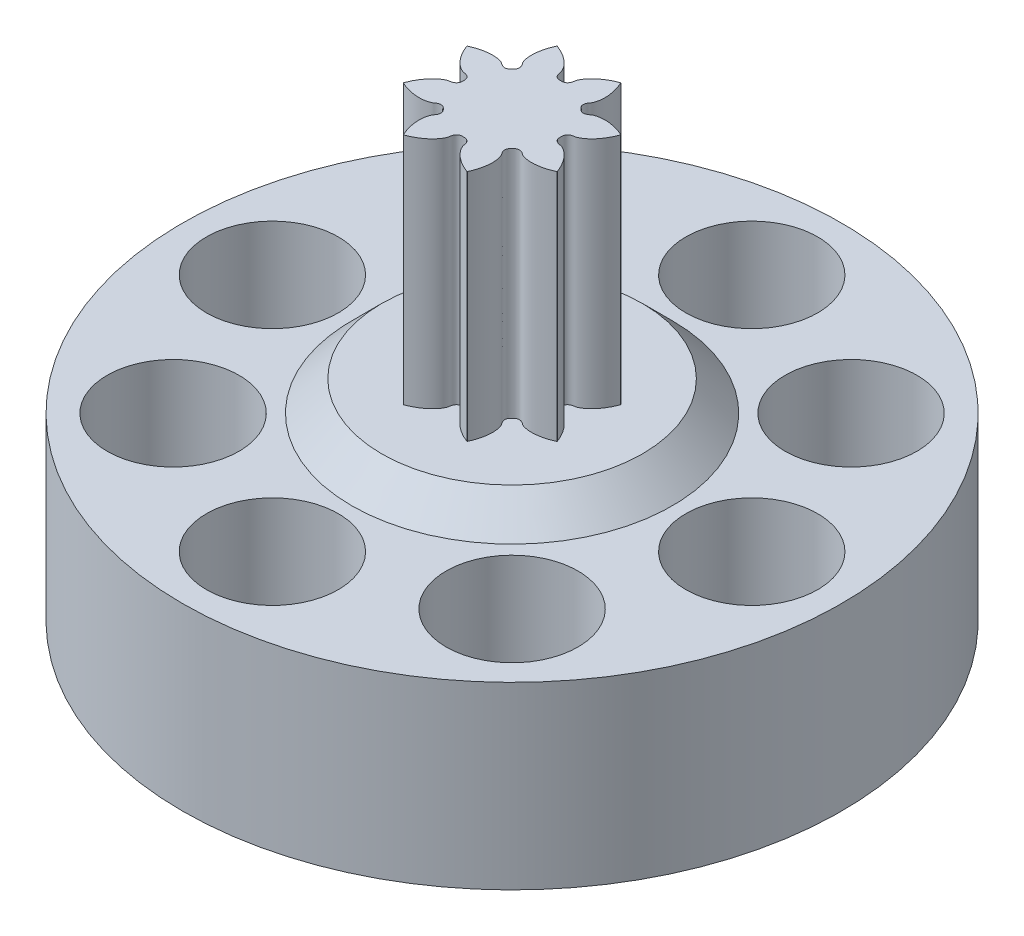
SolidWorks part; units mm, degrees
ref_plane "Front Plane" through (0, 0, 0) normal (0, 0, 1) x (1, 0, 0)
ref_plane "Top Plane" through (0, 0, 0) normal (0, 1, 0) x (1, 0, 0)
ref_plane "Right Plane" through (0, 0, 0) normal (1, 0, 0) x (0, 0, -1)
sketch "Sketch1" plane through (0, 0, 0) normal (0, 1, 0) x (1, 0, 0)
  circle A0 centre (0, 0) radius 11
  dimension "D1" = 22
extrude "Boss-Extrude1" add sketch "Sketch1" along normal mid plane 6
sketch "Sketch2" plane through (0, 3, 0) normal (0, 1, 0) x (1, 0, 0)
  circle A0 centre (0, 8) radius 1
  circle A1 centre (-5.6569, 5.6569) radius 1
  circle A2 centre (5.6569, 5.6569) radius 1
  circle A3 centre (-5.6569, -5.6569) radius 1
  circle A4 centre (5.6569, -5.6569) radius 1
  circle A5 centre (-8, 0) radius 1
  circle A6 centre (0, -8) radius 1
  circle A7 centre (8, 0) radius 1
  circle A8 centre (0, 0) radius 4
  circle A9 centre (0, 0) radius 11
sketch "Sketch5" plane through (0, 3, 0) normal (0, 1, 0) x (1, 0, 0)
  line L0 (2.5656, 1.0576) -> (2.562, 1.0663)
  line L1 (1.0663, 2.562) -> (1.0576, 2.5656)
  line L2 (-1.0576, 2.5656) -> (-1.0663, 2.562)
  line L3 (-2.562, 1.0663) -> (-2.5656, 1.0576)
  line L4 (-2.5656, -1.0576) -> (-2.562, -1.0663)
  line L5 (-1.0663, -2.562) -> (-1.0576, -2.5656)
  line L6 (1.0576, -2.5656) -> (1.0663, -2.562)
  line L7 (2.562, -1.0663) -> (2.5656, -1.0576)
  circle A1 centre (0, 0) radius 2.8
  spline S0 degree 3 poles (2.5656, 1.0576) (2.5467, 1.0063) (2.5127, 0.9243) (2.4586, 0.8162) (2.4108, 0.7326) (2.3616, 0.6567) (2.3117, 0.5883) (2.2618, 0.5274) (2.2125, 0.4736) (2.1645, 0.4267) (2.1184, 0.3865) (2.0746, 0.3524) (2.0339, 0.3241) (1.9966, 0.3012) (1.9632, 0.2831) (1.9342, 0.2695) (1.9099, 0.2596) (1.8905, 0.253) (1.8694, 0.2467) (1.8487, 0.2452) (1.828, 0.2423) (1.8074, 0.2387) (1.7821, 0.2325) (1.7521, 0.2221) (1.7278, 0.2103) (1.7086, 0.1983) (1.6939, 0.1875) (1.6793, 0.1746) (1.665, 0.1592) (1.6515, 0.1408) (1.6395, 0.1191) (1.6301, 0.0941) (1.6246, 0.0677) (1.6231, 0.036) (1.6249, 0) (1.6231, -0.036) (1.6246, -0.0677) (1.6301, -0.0941) (1.6395, -0.1191) (1.6515, -0.1408) (1.665, -0.1592) (1.6793, -0.1746) (1.6982, -0.1913) (1.7224, -0.2076) (1.7521, -0.2221) (1.7821, -0.2325) (1.8074, -0.2387) (1.828, -0.2423) (1.8487, -0.2452) (1.8694, -0.2467) (1.8905, -0.253) (1.9099, -0.2596) (1.9342, -0.2695) (1.9632, -0.2831) (1.9966, -0.3012) (2.0339, -0.3241) (2.0746, -0.3524) (2.1184, -0.3865) (2.1645, -0.4267) (2.2125, -0.4736) (2.2618, -0.5274) (2.3117, -0.5883) (2.3616, -0.6567) (2.4108, -0.7326) (2.4586, -0.8162) (2.5127, -0.9243) (2.5467, -1.0063) (2.5656, -1.0576) knots 0.018496 0.018496 0.018496 0.018496 0.071158 0.103928 0.134826 0.16385 0.191003 0.216283 0.23969 0.261224 0.280886 0.298676 0.314593 0.328637 0.340809 0.351108 0.359535 0.366089 0.37077 0.380767 0.385886 0.390938 0.400931 0.410975 0.421412 0.426928 0.432746 0.438959 0.445665 0.452957 0.460893 0.469469 0.478579 0.486756 0.5 0.513244 0.521421 0.530531 0.539107 0.547043 0.554335 0.561041 0.567254 0.578588 0.589025 0.599069 0.609062 0.614114 0.619233 0.62923 0.633911 0.640465 0.648892 0.659191 0.671363 0.685407 0.701324 0.719114 0.738776 0.76031 0.783717 0.808997 0.83615 0.865174 0.896072 0.928842 0.981504 0.981504 0.981504 0.981504
  spline S1 degree 3 poles (1.0663, 2.562) (1.0892, 2.5123) (1.1232, 2.4303) (1.1614, 2.3156) (1.1867, 2.2227) (1.2056, 2.1343) (1.2186, 2.0507) (1.2264, 1.9723) (1.2296, 1.8994) (1.2288, 1.8323) (1.2246, 1.7712) (1.2178, 1.7162) (1.209, 1.6673) (1.1988, 1.6248) (1.188, 1.5884) (1.1771, 1.5582) (1.1669, 1.534) (1.1579, 1.5157) (1.1474, 1.4963) (1.1339, 1.4806) (1.1212, 1.464) (1.1092, 1.4468) (1.0957, 1.4245) (1.0819, 1.396) (1.0731, 1.3704) (1.0679, 1.3484) (1.0652, 1.3304) (1.0639, 1.3109) (1.0647, 1.2899) (1.0682, 1.2673) (1.0751, 1.2435) (1.0861, 1.2192) (1.1009, 1.1966) (1.1223, 1.1732) (1.149, 1.149) (1.1732, 1.1223) (1.1966, 1.1009) (1.2192, 1.0861) (1.2435, 1.0751) (1.2673, 1.0682) (1.2899, 1.0647) (1.3109, 1.0639) (1.3361, 1.0655) (1.3647, 1.0711) (1.396, 1.0819) (1.4245, 1.0957) (1.4468, 1.1092) (1.464, 1.1212) (1.4806, 1.1339) (1.4963, 1.1474) (1.5157, 1.1579) (1.534, 1.1669) (1.5582, 1.1771) (1.5884, 1.188) (1.6248, 1.1988) (1.6673, 1.209) (1.7162, 1.2178) (1.7712, 1.2246) (1.8323, 1.2288) (1.8994, 1.2296) (1.9723, 1.2264) (2.0507, 1.2186) (2.1343, 1.2056) (2.2227, 1.1867) (2.3156, 1.1614) (2.4303, 1.1232) (2.5123, 1.0892) (2.562, 1.0663) knots 0.018496 0.018496 0.018496 0.018496 0.071158 0.103928 0.134826 0.16385 0.191003 0.216283 0.23969 0.261224 0.280886 0.298676 0.314593 0.328637 0.340809 0.351108 0.359535 0.366089 0.37077 0.380767 0.385886 0.390938 0.400931 0.410975 0.421412 0.426928 0.432746 0.438959 0.445665 0.452957 0.460893 0.469469 0.478579 0.486756 0.5 0.513244 0.521421 0.530531 0.539107 0.547043 0.554335 0.561041 0.567254 0.578588 0.589025 0.599069 0.609062 0.614114 0.619233 0.62923 0.633911 0.640465 0.648892 0.659191 0.671363 0.685407 0.701324 0.719114 0.738776 0.76031 0.783717 0.808997 0.83615 0.865174 0.896072 0.928842 0.981504 0.981504 0.981504 0.981504
  spline S2 degree 3 poles (-1.0576, 2.5656) (-1.0063, 2.5467) (-0.9243, 2.5127) (-0.8162, 2.4586) (-0.7326, 2.4108) (-0.6567, 2.3616) (-0.5883, 2.3117) (-0.5274, 2.2618) (-0.4736, 2.2125) (-0.4267, 2.1645) (-0.3865, 2.1184) (-0.3524, 2.0746) (-0.3241, 2.0339) (-0.3012, 1.9966) (-0.2831, 1.9632) (-0.2695, 1.9342) (-0.2596, 1.9099) (-0.253, 1.8905) (-0.2467, 1.8694) (-0.2452, 1.8487) (-0.2423, 1.828) (-0.2387, 1.8074) (-0.2325, 1.7821) (-0.2221, 1.7521) (-0.2103, 1.7278) (-0.1983, 1.7086) (-0.1875, 1.6939) (-0.1746, 1.6793) (-0.1592, 1.665) (-0.1408, 1.6515) (-0.1191, 1.6395) (-0.0941, 1.6301) (-0.0677, 1.6246) (-0.036, 1.6231) (0, 1.6249) (0.036, 1.6231) (0.0677, 1.6246) (0.0941, 1.6301) (0.1191, 1.6395) (0.1408, 1.6515) (0.1592, 1.665) (0.1746, 1.6793) (0.1913, 1.6982) (0.2076, 1.7224) (0.2221, 1.7521) (0.2325, 1.7821) (0.2387, 1.8074) (0.2423, 1.828) (0.2452, 1.8487) (0.2467, 1.8694) (0.253, 1.8905) (0.2596, 1.9099) (0.2695, 1.9342) (0.2831, 1.9632) (0.3012, 1.9966) (0.3241, 2.0339) (0.3524, 2.0746) (0.3865, 2.1184) (0.4267, 2.1645) (0.4736, 2.2125) (0.5274, 2.2618) (0.5883, 2.3117) (0.6567, 2.3616) (0.7326, 2.4108) (0.8162, 2.4586) (0.9243, 2.5127) (1.0063, 2.5467) (1.0576, 2.5656) knots 0.018496 0.018496 0.018496 0.018496 0.071158 0.103928 0.134826 0.16385 0.191003 0.216283 0.23969 0.261224 0.280886 0.298676 0.314593 0.328637 0.340809 0.351108 0.359535 0.366089 0.37077 0.380767 0.385886 0.390938 0.400931 0.410975 0.421412 0.426928 0.432746 0.438959 0.445665 0.452957 0.460893 0.469469 0.478579 0.486756 0.5 0.513244 0.521421 0.530531 0.539107 0.547043 0.554335 0.561041 0.567254 0.578588 0.589025 0.599069 0.609062 0.614114 0.619233 0.62923 0.633911 0.640465 0.648892 0.659191 0.671363 0.685407 0.701324 0.719114 0.738776 0.76031 0.783717 0.808997 0.83615 0.865174 0.896072 0.928842 0.981504 0.981504 0.981504 0.981504
  spline S3 degree 3 poles (-2.562, 1.0663) (-2.5123, 1.0892) (-2.4303, 1.1232) (-2.3156, 1.1614) (-2.2227, 1.1867) (-2.1343, 1.2056) (-2.0507, 1.2186) (-1.9723, 1.2264) (-1.8994, 1.2296) (-1.8323, 1.2288) (-1.7712, 1.2246) (-1.7162, 1.2178) (-1.6673, 1.209) (-1.6248, 1.1988) (-1.5884, 1.188) (-1.5582, 1.1771) (-1.534, 1.1669) (-1.5157, 1.1579) (-1.4963, 1.1474) (-1.4806, 1.1339) (-1.464, 1.1212) (-1.4468, 1.1092) (-1.4245, 1.0957) (-1.396, 1.0819) (-1.3704, 1.0731) (-1.3484, 1.0679) (-1.3304, 1.0652) (-1.3109, 1.0639) (-1.2899, 1.0647) (-1.2673, 1.0682) (-1.2435, 1.0751) (-1.2192, 1.0861) (-1.1966, 1.1009) (-1.1732, 1.1223) (-1.149, 1.149) (-1.1223, 1.1732) (-1.1009, 1.1966) (-1.0861, 1.2192) (-1.0751, 1.2435) (-1.0682, 1.2673) (-1.0647, 1.2899) (-1.0639, 1.3109) (-1.0655, 1.3361) (-1.0711, 1.3647) (-1.0819, 1.396) (-1.0957, 1.4245) (-1.1092, 1.4468) (-1.1212, 1.464) (-1.1339, 1.4806) (-1.1474, 1.4963) (-1.1579, 1.5157) (-1.1669, 1.534) (-1.1771, 1.5582) (-1.188, 1.5884) (-1.1988, 1.6248) (-1.209, 1.6673) (-1.2178, 1.7162) (-1.2246, 1.7712) (-1.2288, 1.8323) (-1.2296, 1.8994) (-1.2264, 1.9723) (-1.2186, 2.0507) (-1.2056, 2.1343) (-1.1867, 2.2227) (-1.1614, 2.3156) (-1.1232, 2.4303) (-1.0892, 2.5123) (-1.0663, 2.562) knots 0.018496 0.018496 0.018496 0.018496 0.071158 0.103928 0.134826 0.16385 0.191003 0.216283 0.23969 0.261224 0.280886 0.298676 0.314593 0.328637 0.340809 0.351108 0.359535 0.366089 0.37077 0.380767 0.385886 0.390938 0.400931 0.410975 0.421412 0.426928 0.432746 0.438959 0.445665 0.452957 0.460893 0.469469 0.478579 0.486756 0.5 0.513244 0.521421 0.530531 0.539107 0.547043 0.554335 0.561041 0.567254 0.578588 0.589025 0.599069 0.609062 0.614114 0.619233 0.62923 0.633911 0.640465 0.648892 0.659191 0.671363 0.685407 0.701324 0.719114 0.738776 0.76031 0.783717 0.808997 0.83615 0.865174 0.896072 0.928842 0.981504 0.981504 0.981504 0.981504
  spline S4 degree 3 poles (-2.5656, -1.0576) (-2.5467, -1.0063) (-2.5127, -0.9243) (-2.4586, -0.8162) (-2.4108, -0.7326) (-2.3616, -0.6567) (-2.3117, -0.5883) (-2.2618, -0.5274) (-2.2125, -0.4736) (-2.1645, -0.4267) (-2.1184, -0.3865) (-2.0746, -0.3524) (-2.0339, -0.3241) (-1.9966, -0.3012) (-1.9632, -0.2831) (-1.9342, -0.2695) (-1.9099, -0.2596) (-1.8905, -0.253) (-1.8694, -0.2467) (-1.8487, -0.2452) (-1.828, -0.2423) (-1.8074, -0.2387) (-1.7821, -0.2325) (-1.7521, -0.2221) (-1.7278, -0.2103) (-1.7086, -0.1983) (-1.6939, -0.1875) (-1.6793, -0.1746) (-1.665, -0.1592) (-1.6515, -0.1408) (-1.6395, -0.1191) (-1.6301, -0.0941) (-1.6246, -0.0677) (-1.6231, -0.036) (-1.6249, 0) (-1.6231, 0.036) (-1.6246, 0.0677) (-1.6301, 0.0941) (-1.6395, 0.1191) (-1.6515, 0.1408) (-1.665, 0.1592) (-1.6793, 0.1746) (-1.6982, 0.1913) (-1.7224, 0.2076) (-1.7521, 0.2221) (-1.7821, 0.2325) (-1.8074, 0.2387) (-1.828, 0.2423) (-1.8487, 0.2452) (-1.8694, 0.2467) (-1.8905, 0.253) (-1.9099, 0.2596) (-1.9342, 0.2695) (-1.9632, 0.2831) (-1.9966, 0.3012) (-2.0339, 0.3241) (-2.0746, 0.3524) (-2.1184, 0.3865) (-2.1645, 0.4267) (-2.2125, 0.4736) (-2.2618, 0.5274) (-2.3117, 0.5883) (-2.3616, 0.6567) (-2.4108, 0.7326) (-2.4586, 0.8162) (-2.5127, 0.9243) (-2.5467, 1.0063) (-2.5656, 1.0576) knots 0.018496 0.018496 0.018496 0.018496 0.071158 0.103928 0.134826 0.16385 0.191003 0.216283 0.23969 0.261224 0.280886 0.298676 0.314593 0.328637 0.340809 0.351108 0.359535 0.366089 0.37077 0.380767 0.385886 0.390938 0.400931 0.410975 0.421412 0.426928 0.432746 0.438959 0.445665 0.452957 0.460893 0.469469 0.478579 0.486756 0.5 0.513244 0.521421 0.530531 0.539107 0.547043 0.554335 0.561041 0.567254 0.578588 0.589025 0.599069 0.609062 0.614114 0.619233 0.62923 0.633911 0.640465 0.648892 0.659191 0.671363 0.685407 0.701324 0.719114 0.738776 0.76031 0.783717 0.808997 0.83615 0.865174 0.896072 0.928842 0.981504 0.981504 0.981504 0.981504
  spline S5 degree 3 poles (-1.0663, -2.562) (-1.0892, -2.5123) (-1.1232, -2.4303) (-1.1614, -2.3156) (-1.1867, -2.2227) (-1.2056, -2.1343) (-1.2186, -2.0507) (-1.2264, -1.9723) (-1.2296, -1.8994) (-1.2288, -1.8323) (-1.2246, -1.7712) (-1.2178, -1.7162) (-1.209, -1.6673) (-1.1988, -1.6248) (-1.188, -1.5884) (-1.1771, -1.5582) (-1.1669, -1.534) (-1.1579, -1.5157) (-1.1474, -1.4963) (-1.1339, -1.4806) (-1.1212, -1.464) (-1.1092, -1.4468) (-1.0957, -1.4245) (-1.0819, -1.396) (-1.0731, -1.3704) (-1.0679, -1.3484) (-1.0652, -1.3304) (-1.0639, -1.3109) (-1.0647, -1.2899) (-1.0682, -1.2673) (-1.0751, -1.2435) (-1.0861, -1.2192) (-1.1009, -1.1966) (-1.1223, -1.1732) (-1.149, -1.149) (-1.1732, -1.1223) (-1.1966, -1.1009) (-1.2192, -1.0861) (-1.2435, -1.0751) (-1.2673, -1.0682) (-1.2899, -1.0647) (-1.3109, -1.0639) (-1.3361, -1.0655) (-1.3647, -1.0711) (-1.396, -1.0819) (-1.4245, -1.0957) (-1.4468, -1.1092) (-1.464, -1.1212) (-1.4806, -1.1339) (-1.4963, -1.1474) (-1.5157, -1.1579) (-1.534, -1.1669) (-1.5582, -1.1771) (-1.5884, -1.188) (-1.6248, -1.1988) (-1.6673, -1.209) (-1.7162, -1.2178) (-1.7712, -1.2246) (-1.8323, -1.2288) (-1.8994, -1.2296) (-1.9723, -1.2264) (-2.0507, -1.2186) (-2.1343, -1.2056) (-2.2227, -1.1867) (-2.3156, -1.1614) (-2.4303, -1.1232) (-2.5123, -1.0892) (-2.562, -1.0663) knots 0.018496 0.018496 0.018496 0.018496 0.071158 0.103928 0.134826 0.16385 0.191003 0.216283 0.23969 0.261224 0.280886 0.298676 0.314593 0.328637 0.340809 0.351108 0.359535 0.366089 0.37077 0.380767 0.385886 0.390938 0.400931 0.410975 0.421412 0.426928 0.432746 0.438959 0.445665 0.452957 0.460893 0.469469 0.478579 0.486756 0.5 0.513244 0.521421 0.530531 0.539107 0.547043 0.554335 0.561041 0.567254 0.578588 0.589025 0.599069 0.609062 0.614114 0.619233 0.62923 0.633911 0.640465 0.648892 0.659191 0.671363 0.685407 0.701324 0.719114 0.738776 0.76031 0.783717 0.808997 0.83615 0.865174 0.896072 0.928842 0.981504 0.981504 0.981504 0.981504
  spline S6 degree 3 poles (1.0576, -2.5656) (1.0063, -2.5467) (0.9243, -2.5127) (0.8162, -2.4586) (0.7326, -2.4108) (0.6567, -2.3616) (0.5883, -2.3117) (0.5274, -2.2618) (0.4736, -2.2125) (0.4267, -2.1645) (0.3865, -2.1184) (0.3524, -2.0746) (0.3241, -2.0339) (0.3012, -1.9966) (0.2831, -1.9632) (0.2695, -1.9342) (0.2596, -1.9099) (0.253, -1.8905) (0.2467, -1.8694) (0.2452, -1.8487) (0.2423, -1.828) (0.2387, -1.8074) (0.2325, -1.7821) (0.2221, -1.7521) (0.2103, -1.7278) (0.1983, -1.7086) (0.1875, -1.6939) (0.1746, -1.6793) (0.1592, -1.665) (0.1408, -1.6515) (0.1191, -1.6395) (0.0941, -1.6301) (0.0677, -1.6246) (0.036, -1.6231) (0, -1.6249) (-0.036, -1.6231) (-0.0677, -1.6246) (-0.0941, -1.6301) (-0.1191, -1.6395) (-0.1408, -1.6515) (-0.1592, -1.665) (-0.1746, -1.6793) (-0.1913, -1.6982) (-0.2076, -1.7224) (-0.2221, -1.7521) (-0.2325, -1.7821) (-0.2387, -1.8074) (-0.2423, -1.828) (-0.2452, -1.8487) (-0.2467, -1.8694) (-0.253, -1.8905) (-0.2596, -1.9099) (-0.2695, -1.9342) (-0.2831, -1.9632) (-0.3012, -1.9966) (-0.3241, -2.0339) (-0.3524, -2.0746) (-0.3865, -2.1184) (-0.4267, -2.1645) (-0.4736, -2.2125) (-0.5274, -2.2618) (-0.5883, -2.3117) (-0.6567, -2.3616) (-0.7326, -2.4108) (-0.8162, -2.4586) (-0.9243, -2.5127) (-1.0063, -2.5467) (-1.0576, -2.5656) knots 0.018496 0.018496 0.018496 0.018496 0.071158 0.103928 0.134826 0.16385 0.191003 0.216283 0.23969 0.261224 0.280886 0.298676 0.314593 0.328637 0.340809 0.351108 0.359535 0.366089 0.37077 0.380767 0.385886 0.390938 0.400931 0.410975 0.421412 0.426928 0.432746 0.438959 0.445665 0.452957 0.460893 0.469469 0.478579 0.486756 0.5 0.513244 0.521421 0.530531 0.539107 0.547043 0.554335 0.561041 0.567254 0.578588 0.589025 0.599069 0.609062 0.614114 0.619233 0.62923 0.633911 0.640465 0.648892 0.659191 0.671363 0.685407 0.701324 0.719114 0.738776 0.76031 0.783717 0.808997 0.83615 0.865174 0.896072 0.928842 0.981504 0.981504 0.981504 0.981504
  spline S7 degree 3 poles (2.562, -1.0663) (2.5123, -1.0892) (2.4303, -1.1232) (2.3156, -1.1614) (2.2227, -1.1867) (2.1343, -1.2056) (2.0507, -1.2186) (1.9723, -1.2264) (1.8994, -1.2296) (1.8323, -1.2288) (1.7712, -1.2246) (1.7162, -1.2178) (1.6673, -1.209) (1.6248, -1.1988) (1.5884, -1.188) (1.5582, -1.1771) (1.534, -1.1669) (1.5157, -1.1579) (1.4963, -1.1474) (1.4806, -1.1339) (1.464, -1.1212) (1.4468, -1.1092) (1.4245, -1.0957) (1.396, -1.0819) (1.3704, -1.0731) (1.3484, -1.0679) (1.3304, -1.0652) (1.3109, -1.0639) (1.2899, -1.0647) (1.2673, -1.0682) (1.2435, -1.0751) (1.2192, -1.0861) (1.1966, -1.1009) (1.1732, -1.1223) (1.149, -1.149) (1.1223, -1.1732) (1.1009, -1.1966) (1.0861, -1.2192) (1.0751, -1.2435) (1.0682, -1.2673) (1.0647, -1.2899) (1.0639, -1.3109) (1.0655, -1.3361) (1.0711, -1.3647) (1.0819, -1.396) (1.0957, -1.4245) (1.1092, -1.4468) (1.1212, -1.464) (1.1339, -1.4806) (1.1474, -1.4963) (1.1579, -1.5157) (1.1669, -1.534) (1.1771, -1.5582) (1.188, -1.5884) (1.1988, -1.6248) (1.209, -1.6673) (1.2178, -1.7162) (1.2246, -1.7712) (1.2288, -1.8323) (1.2296, -1.8994) (1.2264, -1.9723) (1.2186, -2.0507) (1.2056, -2.1343) (1.1867, -2.2227) (1.1614, -2.3156) (1.1232, -2.4303) (1.0892, -2.5123) (1.0663, -2.562) knots 0.018496 0.018496 0.018496 0.018496 0.071158 0.103928 0.134826 0.16385 0.191003 0.216283 0.23969 0.261224 0.280886 0.298676 0.314593 0.328637 0.340809 0.351108 0.359535 0.366089 0.37077 0.380767 0.385886 0.390938 0.400931 0.410975 0.421412 0.426928 0.432746 0.438959 0.445665 0.452957 0.460893 0.469469 0.478579 0.486756 0.5 0.513244 0.521421 0.530531 0.539107 0.547043 0.554335 0.561041 0.567254 0.578588 0.589025 0.599069 0.609062 0.614114 0.619233 0.62923 0.633911 0.640465 0.648892 0.659191 0.671363 0.685407 0.701324 0.719114 0.738776 0.76031 0.783717 0.808997 0.83615 0.865174 0.896072 0.928842 0.981504 0.981504 0.981504 0.981504
  dimension "D2" = 5.6
extrude "Boss-Extrude2" add sketch "Sketch5" along normal blind 8.8 contours S7 L7 S0 L0 S1 L1 S2 L2 S3 L3 S4 L4 S5 L5 S6 L6 region at (0, 3, 0)
hole_wizard "CBORE for M2 SHCS3" positions "Sketch11" profile "Sketch13" counterbore size "M2" standard "ANSI Metric"
sketch "Sketch11" plane through (0, 3, 0) normal (0, 1, 0) x (1, 0, 0)
  point P0 (-8, 0)
  point P3 (-5.6569, 5.6569)
  point P6 (0, 8)
  point P9 (5.6569, 5.6569)
  point P12 (8, 0)
  point P15 (5.6569, -5.6569)
  point P18 (0, -8)
  point P21 (-5.6569, -5.6569)
sketch "Sketch13" plane through (-8, 3, 0) normal (1, 0, 0) x (0, 0, 1)
  line L0 (0, 0) -> (0, 6.7811)
  line L1 (0, 6.7811) -> (1.3, 6)
  line L2 (1.3, 6) -> (1.3, 5)
  line L3 (1.3, 5) -> (2.2, 5)
  line L4 (2.2, 5) -> (2.2, 0)
  line L5 (2.2, 0) -> (0, 0)
  line L10 (0, 6.7811) -> (-1.3, 6) construction
  line L11 (0, -6.35) -> (0, 107.95) construction
  dimension "Hole Dia." = 2.6
  dimension "Hole Depth" = 6
  dimension "C'Bore Dia." = 4.4
  dimension "C'Bore Depth" = 5
  dimension "Drill Angle" = 118
sketch "Sketch14" plane through (0, -3, 0) normal (0, -1, 0) x (1, 0, 0)
  circle A0 centre (0, 0) radius 4.2
  dimension "D1" = 8.4
extrude "Cut-Extrude4" cut sketch "Sketch14" against normal blind 5.95
sketch "Sketch15" plane through (0, 3, 0) normal (0, 1, 0) x (1, 0, 0)
  circle A0 centre (0, 0) radius 4.35
  dimension "D1" = 8.7
extrude "Boss-Extrude4" add sketch "Sketch15" along normal blind 1
chamfer "Chamfer1" distance 1 angle 45 1 edges at (0, 3, 4.35)
